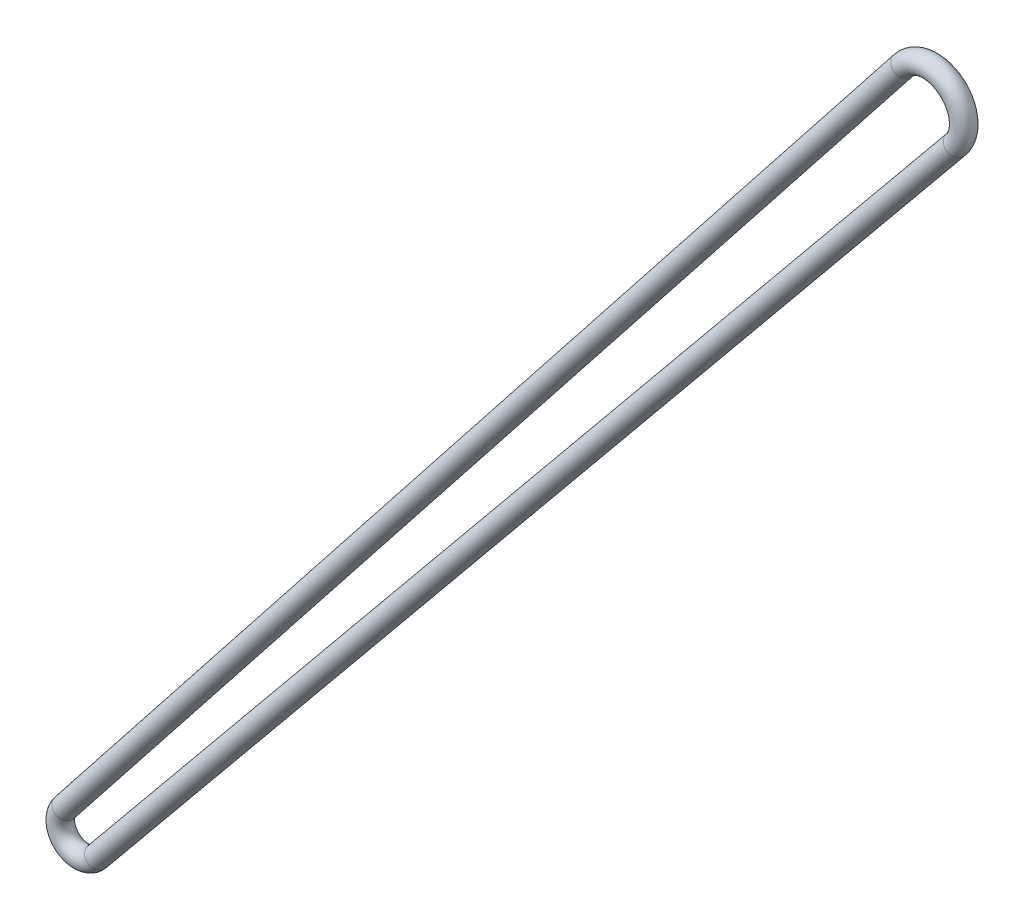
SolidWorks part; units mm, degrees
ref_plane "前视基准面" through (0, 0, 0) normal (0, 0, 1) x (1, 0, 0)
ref_plane "上视基准面" through (0, 0, 0) normal (0, 1, 0) x (1, 0, 0)
ref_plane "右视基准面" through (0, 0, 0) normal (1, 0, 0) x (0, 0, -1)
sketch "草图2" plane through (0, 0, 0) normal (0, 0, 1) x (1, 0, 0)
  line L0 (0, 0) -> (1, 0) construction
  line L1 (0, 0) -> (0, 1) construction
  line L2 (-2.4329, 1.9212) -> (121.9894, 159.4874)
  line L3 (129.7782, 153.2164) -> (2.3961, -1.9669)
  arc A0 (2.3961, -1.9669) -> (-2.4329, 1.9212) centre (0, 0) cw
  arc A1 (121.9894, 159.4874) -> (129.7782, 153.2164) centre (125.9135, 156.3887) cw
sweep "扫描19" add path "草图2" circular profile diameter 3 parameters "D3"=3
